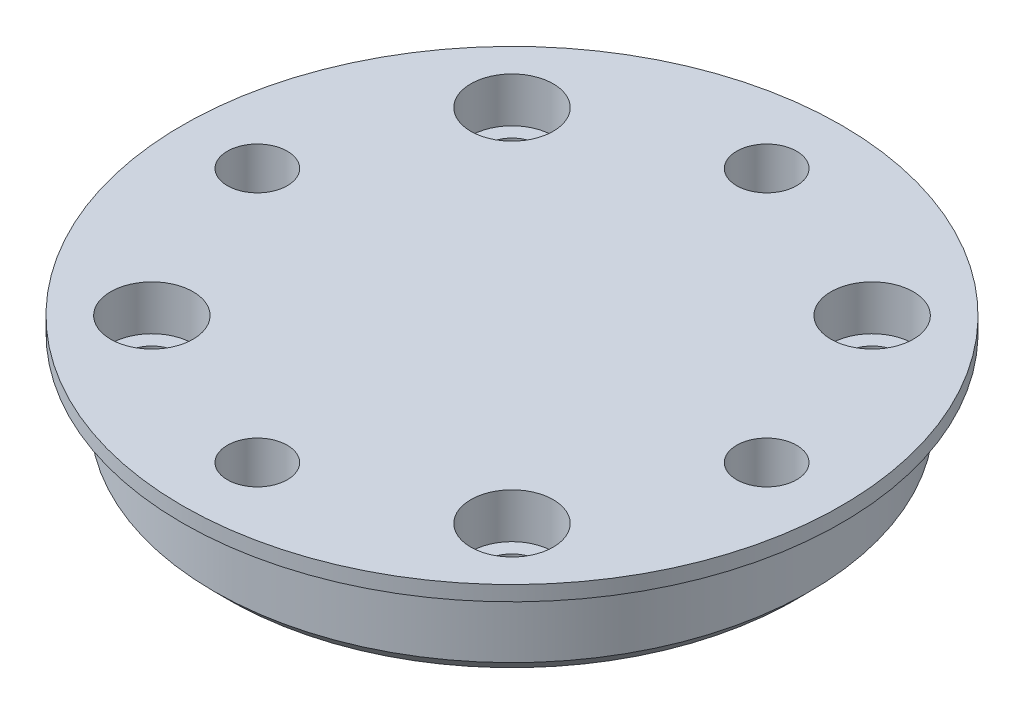
SolidWorks part; units mm, degrees
ref_plane "Front Plane" through (0, 0, 0) normal (0, 0, 1) x (1, 0, 0)
ref_plane "Top Plane" through (0, 0, 0) normal (0, 1, 0) x (1, 0, 0)
ref_plane "Right Plane" through (0, 0, 0) normal (1, 0, 0) x (0, 0, -1)
sketch "Sketch1" plane through (0, 0, 0) normal (0, 1, 0) x (1, 0, 0)
  circle A0 centre (0, 0) radius 19.9
  dimension "D1" = 39.8
extrude "Boss-Extrude1" add sketch "Sketch1" along normal blind 6
sketch "Sketch2" plane through (0, 6, 0) normal (0, 1, 0) x (1, 0, 0)
  circle A0 centre (0, 0) radius 22
  dimension "D1" = 44
extrude "Boss-Extrude2" add sketch "Sketch2" along normal blind 1
sketch "Sketch3" plane through (0, 7, 0) normal (0, 1, 0) x (1, 0, 0)
  line L0 (0, 0) -> (0, 17) construction
  line L1 (0, 0) -> (-12.0208, 12.0208) construction
  circle A0 centre (0, 17) radius 2
  circle A1 centre (17, 0) radius 2
  circle A2 centre (0, -17) radius 2
  circle A3 centre (-17, 0) radius 2
  circle A4 centre (-12.0208, 12.0208) radius 1.75
  circle A5 centre (12.0208, 12.0208) radius 1.75
  circle A6 centre (12.0208, -12.0208) radius 1.75
  circle A7 centre (-12.0208, -12.0208) radius 1.75
  point P12 (0, 0)
  point P22 (0, 0)
  dimension "D2" = 4
  dimension "D6" = 3.5
  dimension "D1" = 17
  dimension "D4" = 17
  dimension "D5" = 45
  dimension "D3" = 4
  dimension "D7" = 4
extrude "Cut-Extrude1" cut sketch "Sketch3" against normal through all
sketch "Sketch5" plane through (0, 7, 0) normal (0, 1, 0) x (1, 0, 0)
  circle A0 centre (-12.0208, 12.0208) radius 1.75 construction
  circle A1 centre (-12.0208, 12.0208) radius 1.75
  circle A2 centre (-12.0208, 12.0208) radius 2.75
  circle A3 centre (12.0208, 12.0208) radius 2.75
  circle A4 centre (12.0208, 12.0208) radius 1.75
  circle A5 centre (12.0208, -12.0208) radius 2.75
  circle A6 centre (12.0208, -12.0208) radius 1.75
  circle A7 centre (-12.0208, -12.0208) radius 2.75
  circle A8 centre (-12.0208, -12.0208) radius 1.75
  point P20 (0, 0)
  dimension "D1" = 1
  dimension "D2" = 4
extrude "Cut-Extrude2" cut sketch "Sketch5" against normal blind 3
chamfer "Chamfer1" distance 1 angle 45 1 edges at (0, 0, 19.9)
